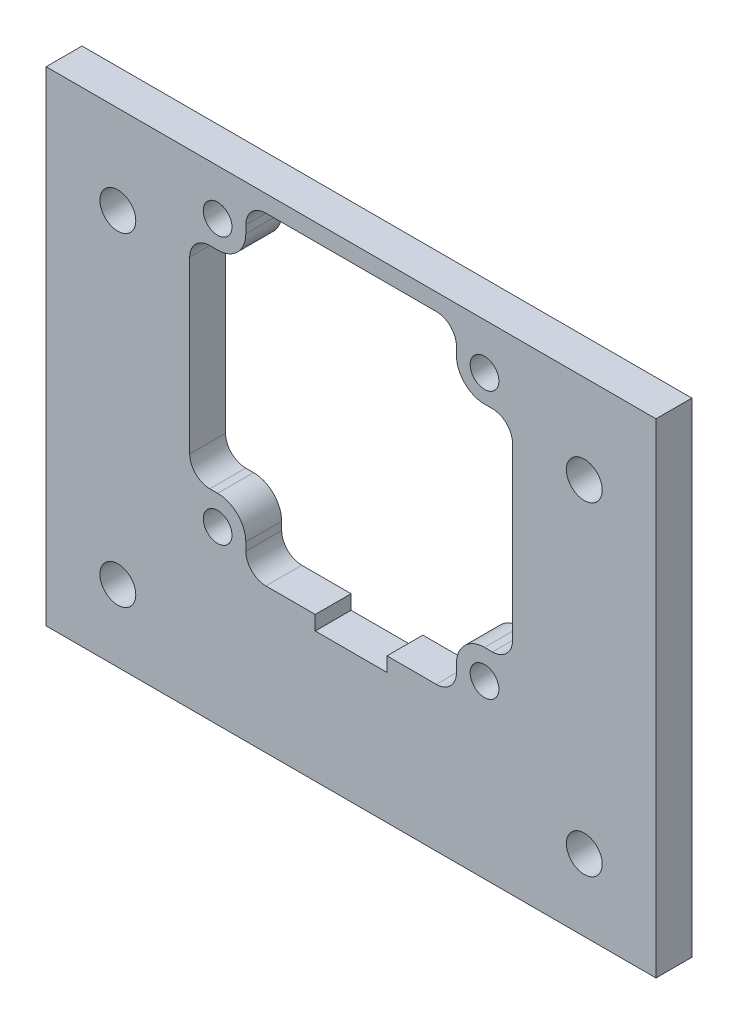
SolidWorks part; units mm, degrees
ref_plane "Front Plane" through (0, 0, 0) normal (0, 0, 1) x (1, 0, 0)
ref_plane "Top Plane" through (0, 0, 0) normal (0, 1, 0) x (1, 0, 0)
ref_plane "Right Plane" through (0, 0, 0) normal (1, 0, 0) x (0, 0, -1)
sketch "Sketch1" plane through (0, 0, 0) normal (0, 0, 1) x (1, 0, 0)
  line L0 (-2.667, -1.7227) -> (-2.667, 1.7227) construction
  line L1 (28.575, -28.575) -> (-28.575, -28.575) construction
  line L2 (28.575, -28.575) -> (28.575, 28.575) construction
  line L3 (28.575, 28.575) -> (-28.575, 28.575) construction
  line L4 (-28.575, -28.575) -> (-28.575, 28.575) construction
  line L5 (28.575, -28.575) -> (-28.575, 28.575) construction
  line L6 (28.575, 28.575) -> (-28.575, -28.575) construction
  line L7 (23.622, -23.622) -> (-23.622, -23.622) construction
  line L8 (23.622, -23.622) -> (23.622, 23.622) construction
  line L9 (23.622, 23.622) -> (-23.622, 23.622) construction
  line L10 (-23.622, -23.622) -> (-23.622, 23.622) construction
  line L11 (23.622, -23.622) -> (-23.622, 23.622) construction
  line L12 (23.622, 23.622) -> (-23.622, -23.622) construction
  line L14 (53.975, 31.75) -> (-53.975, 31.75)
  line L15 (53.975, 31.75) -> (53.975, 0)
  line L16 (53.975, 0) -> (-53.975, 0)
  line L17 (-53.975, 31.75) -> (-53.975, 0)
  line L18 (0, 0) -> (0, 31.75) construction
  line L19 (53.975, 15.875) -> (-53.975, 15.875) construction
  line L20 (53.975, -53.975) -> (-53.975, -53.975)
  line L21 (53.975, -53.975) -> (53.975, 0)
  line L22 (53.975, 0) -> (-53.975, 0)
  line L23 (-53.975, -53.975) -> (-53.975, 0)
  line L24 (0, 0) -> (0, -53.975) construction
  line L25 (53.975, -26.9875) -> (-53.975, -26.9875) construction
  circle A0 centre (-23.622, 23.622) radius 2.54 construction
  circle A1 centre (23.622, 23.622) radius 2.54 construction
  circle A2 centre (-23.622, -23.622) radius 2.54 construction
  circle A3 centre (23.622, -23.622) radius 2.54 construction
  point P0 (0, 0)
  point P6 (0, 0)
  point P15 (0, 0)
  point P16 (0, 15.875)
  point P18 (0, 3.175)
  point P19 (0, 28.575)
  point P20 (0, 19.05)
  point P21 (-23.622, -26.162)
  point P27 (0, -26.9875)
  dimension "D3" = 5.08
  dimension "D4" = 107.95
  dimension "D5" = 53.975
  dimension "D1" = 107.95
  dimension "Width" = 57.15
  dimension "D2" = 31.75
  dimension "CenterToCenter" = 47.244
sketch "Sketch3" plane through (0, 0, 0) normal (0, 0, 1) x (1, 0, 0)
  line L1 (-28.575, -28.575) -> (-28.575, 28.575) construction
  line L2 (28.575, 28.575) -> (-28.575, 28.575) construction
  line L3 (28.575, -28.575) -> (28.575, 28.575) construction
  line L4 (28.575, -28.575) -> (-28.575, -28.575) construction
  line L5 (-28.575, -25.4) -> (-28.575, 25.4)
  line L6 (25.4, 28.575) -> (-25.4, 28.575)
  line L7 (28.575, -25.4) -> (28.575, 25.4)
  line L8 (25.4, -28.575) -> (-25.4, -28.575)
  arc A4 (-28.575, 25.4) -> (-25.4, 28.575) centre (-25.4, 25.4) cw
  arc A5 (25.4, 28.575) -> (28.575, 25.4) centre (25.4, 25.4) cw
  arc A6 (28.575, -25.4) -> (25.4, -28.575) centre (25.4, -25.4) cw
  arc A7 (-25.4, -28.575) -> (-28.575, -25.4) centre (-25.4, -25.4) cw
  dimension "D1" = 3.175
extrude "Boss-Extrude1" add sketch "Sketch1" along normal blind 6.35 contours L14 L17 L16 L15 | L23 L20 L21 L16 region at (0, 15.875, 0) region at (0, -26.9875, 0)
sketch "Sketch11" plane through (0, 0, 0) normal (0, 0, -1) x (-1, 0, 0)
  line L4 (-23.622, 23.622) -> (-23.622, -23.622)
  line L5 (-23.622, -23.622) -> (23.622, -23.622)
  line L6 (-23.622, 23.622) -> (23.622, 23.622)
  line L7 (23.622, 23.622) -> (23.622, -23.622)
  circle A0 centre (23.622, -23.622) radius 2.54
  circle A1 centre (-23.622, -23.622) radius 2.54
  circle A2 centre (-23.622, 23.622) radius 2.54
  circle A3 centre (23.622, 23.622) radius 2.54
  dimension "D1" = 47.244
  dimension "D2" = 47.244
extrude "Cut-Extrude2" cut sketch "Sketch11" against normal blind 7.62 contours A2 | A3 | A0 | A1
sketch "Sketch12" plane through (0, 0, 0) normal (0, 0, -1) x (-1, 0, 0)
  line L0 (-0.0085, 28.7524) -> (-0.0085, 0.1774) construction
  line L1 (-0.0085, 0.1774) -> (-28.5835, 0.1774) construction
  line L2 (-25.0275, 18.821) -> (-23.6305, 18.821)
  line L3 (-18.6521, 23.7994) -> (-18.6521, 25.1964)
  line L4 (-28.5835, 15.265) -> (-28.5835, -14.9102)
  line L5 (15.0791, 28.7524) -> (-15.0961, 28.7524)
  line L6 (28.5665, -14.9102) -> (28.5665, 15.265)
  line L7 (18.6351, 23.7994) -> (18.6351, 25.1964)
  line L8 (25.0105, 18.821) -> (23.6135, 18.821)
  line L9 (25.0105, -18.4662) -> (23.6135, -18.4662)
  line L10 (18.6351, -23.4446) -> (18.6351, -24.8416)
  line L11 (15.0791, -28.3976) -> (-15.0961, -28.3976)
  line L12 (-18.6521, -23.4446) -> (-18.6521, -24.8416)
  line L13 (-25.0275, -18.4662) -> (-23.6305, -18.4662)
  line L15 (-6.3585, -30.9376) -> (6.3415, -30.9376)
  line L16 (-6.3585, -30.9376) -> (-6.3585, -28.3976)
  line L17 (-6.3585, -28.3976) -> (6.3415, -28.3976)
  line L18 (6.3415, -30.9376) -> (6.3415, -28.3976)
  arc A0 (-25.0275, 18.821) -> (-28.5835, 15.265) centre (-25.0275, 15.265) ccw
  arc A1 (-15.0961, 28.7524) -> (-18.6521, 25.1964) centre (-15.0961, 25.1964) ccw
  arc A2 (-23.6305, 18.821) -> (-18.6521, 23.7994) centre (-23.6305, 23.7994) ccw
  arc A3 (23.6135, 18.821) -> (18.6351, 23.7994) centre (23.6135, 23.7994) cw
  arc A4 (15.0791, 28.7524) -> (18.6351, 25.1964) centre (15.0791, 25.1964) cw
  arc A5 (25.0105, 18.821) -> (28.5665, 15.265) centre (25.0105, 15.265) cw
  arc A6 (25.0105, -18.4662) -> (28.5665, -14.9102) centre (25.0105, -14.9102) ccw
  arc A7 (15.0791, -28.3976) -> (18.6351, -24.8416) centre (15.0791, -24.8416) ccw
  arc A8 (23.6135, -18.4662) -> (18.6351, -23.4446) centre (23.6135, -23.4446) ccw
  arc A9 (-23.6305, -18.4662) -> (-18.6521, -23.4446) centre (-23.6305, -23.4446) cw
  arc A10 (-15.0961, -28.3976) -> (-18.6521, -24.8416) centre (-15.0961, -24.8416) cw
  arc A11 (-25.0275, -18.4662) -> (-28.5835, -14.9102) centre (-25.0275, -14.9102) cw
  point P43 (-0.0085, -28.3976)
  point P44 (-0.0085, -28.3976)
  dimension "D3" = 2.54
  dimension "D4" = 12.7
extrude "Cut-Extrude3" cut sketch "Sketch12" against normal blind 7.62 contours A11 L13 A9 L12 A10 L11 A7 L10 A8 L9 A6 L6 A5 L8 A3 L7 A4 L5 A1 L3 A2 L2 A0 L4 | L15 L18 L11 L16 region at (0.0085, 0.1774, 0) region at (0.0085, -29.6676, 0)
sketch "Sketch13" plane through (0, 0, 0) normal (0, 0, -1) x (-1, 0, 0)
  line L0 (-41.2835, 31.75) -> (-41.2835, -53.975) construction
  line L1 (-53.975, 31.75) -> (53.975, 31.75) construction
  line L2 (-53.975, -53.975) -> (53.975, -53.975) construction
  line L3 (-28.5835, 15.265) -> (-28.5835, -14.9102) construction
  line L4 (15.0791, 28.7524) -> (-15.0961, 28.7524) construction
  line L5 (0, 31.75) -> (0, -53.975) construction
  circle A0 centre (-41.2835, 16.0524) radius 3.175
  circle A1 centre (-41.2835, -41.275) radius 3.175
  circle A2 centre (41.2835, -41.275) radius 3.175
  circle A3 centre (41.2835, 16.0524) radius 3.175
  dimension "D1" = 6.35
  dimension "D2" = 12.7
  dimension "D3" = 12.7
  dimension "D4" = 12.7
extrude "Cut-Extrude4" cut sketch "Sketch13" against normal blind 7.62 contours A0 | A1 | A2 | A3
